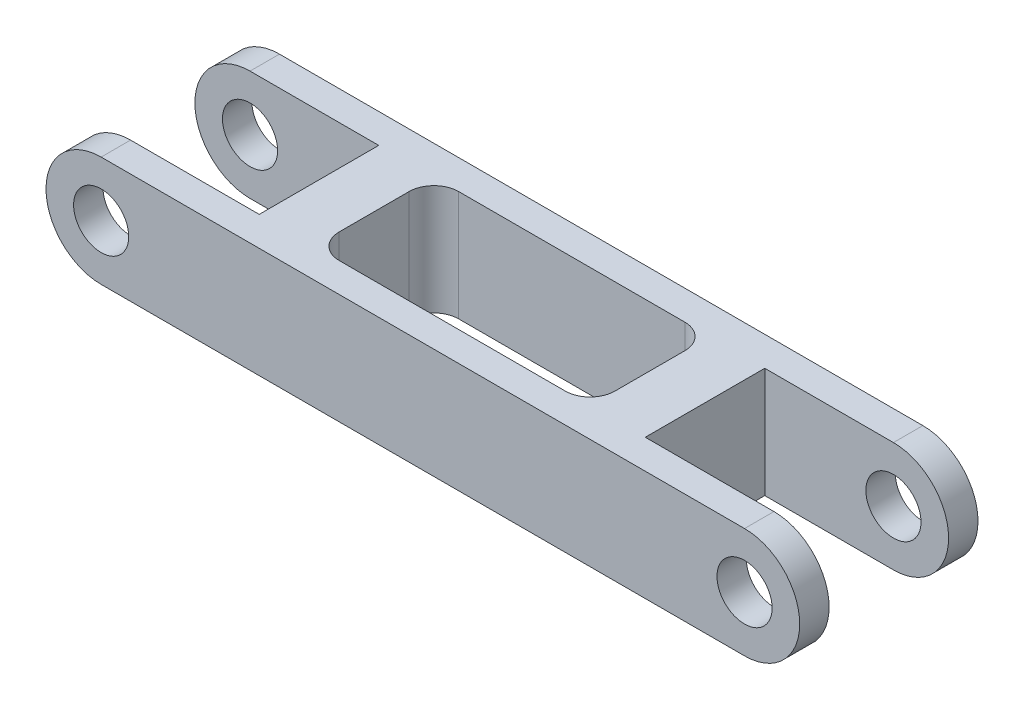
SolidWorks part; units mm, degrees
ref_plane "前视基准面" through (0, 0, 0) normal (0, 0, 1) x (1, 0, 0)
ref_plane "上视基准面" through (0, 0, 0) normal (0, 1, 0) x (1, 0, 0)
ref_plane "右视基准面" through (0, 0, 0) normal (1, 0, 0) x (0, 0, -1)
sketch "草图1" plane through (0, 0, 0) normal (0, 0, 1) x (1, 0, 0)
  line L0 (-35, 0) -> (35, 0) construction
  line L1 (-35, 6) -> (35, 6)
  line L2 (-35, -6) -> (35, -6)
  arc A0 (-35, 6) -> (-35, -6) centre (-35, 0) ccw
  arc A1 (35, -6) -> (35, 6) centre (35, 0) ccw
  circle A2 centre (-35, 0) radius 3
  circle A3 centre (35, 0) radius 3
  point P3 (0, 0)
  dimension "D3" = 6
  dimension "D4" = 6
  dimension "D1" = 12
  dimension "D2" = 70
extrude "凸台-拉伸1" add sketch "草图1" along normal blind 19.4
sketch "草图2" plane through (0, 6, 0) normal (0, 1, 0) x (1, 0, 0)
  line L0 (-35, 0) -> (-41, 0) construction
  line L1 (-41, -3.2) -> (-21, -3.2)
  line L2 (-41, -3.2) -> (-41, -16.2)
  line L3 (-41, -16.2) -> (-21, -16.2)
  line L4 (-21, -3.2) -> (-21, -16.2)
  line L5 (-35, -19.4) -> (-35, 0) construction
  line L6 (0, 0) -> (0, -26.8414) construction
  line L7 (21, -3.2) -> (21, -16.2)
  line L8 (41, -16.2) -> (21, -16.2)
  line L9 (41, -3.2) -> (41, -16.2)
  line L10 (41, -3.2) -> (21, -3.2)
  line L11 (35, 0) -> (-35, 0) construction
  line L12 (-12.3, -3.2) -> (12.3, -3.2)
  line L13 (-15, -5.9) -> (-15, -13.5)
  line L14 (-12.3, -16.2) -> (12.3, -16.2)
  line L15 (15, -5.9) -> (15, -13.5)
  line L16 (35, -19.4) -> (-35, -19.4) construction
  arc A0 (15, -13.5) -> (12.3, -16.2) centre (12.3, -13.5) cw
  arc A1 (15, -5.9) -> (12.3, -3.2) centre (12.3, -5.9) ccw
  arc A2 (-12.3, -16.2) -> (-15, -13.5) centre (-12.3, -13.5) cw
  arc A3 (-12.3, -3.2) -> (-15, -5.9) centre (-12.3, -5.9) ccw
  dimension "D9" = 2.7
  dimension "D1" = 13
  dimension "D2" = 3.2
  dimension "D3" = 6
  dimension "D4" = 20
  dimension "D5" = 6
  dimension "D6" = 6
  dimension "D7" = 3.2
  dimension "D8" = 3.2
extrude "切除-拉伸1" cut sketch "草图2" against normal through all
